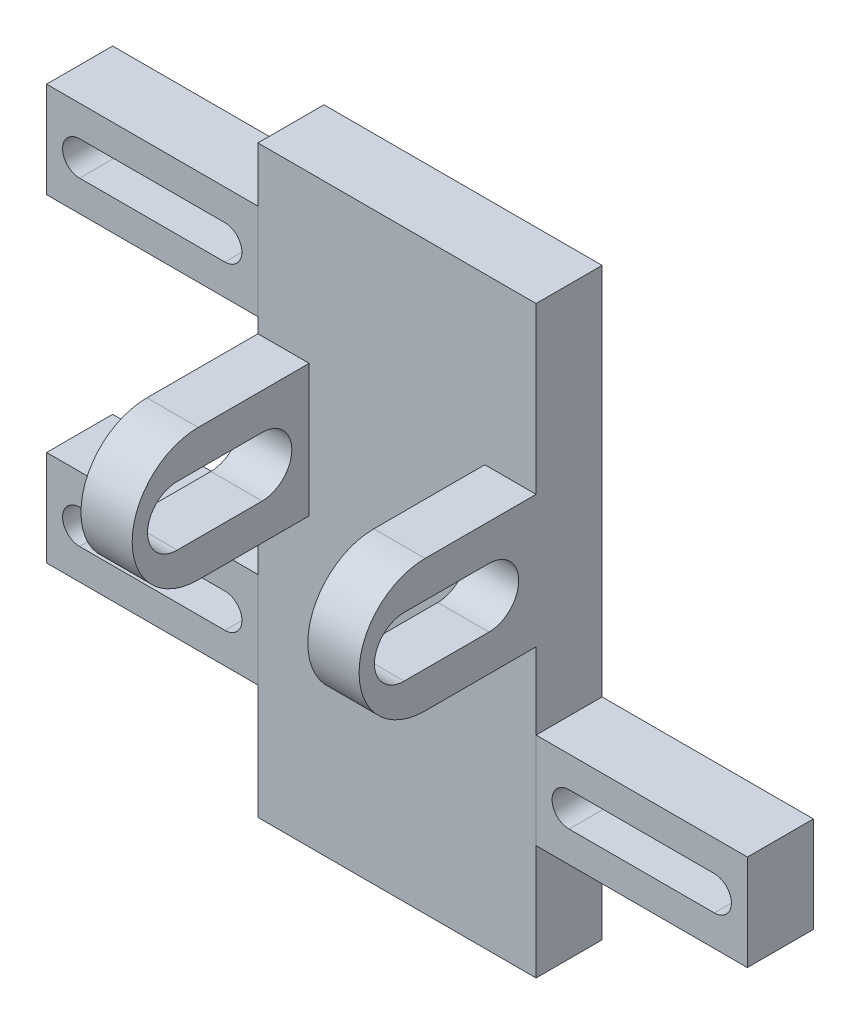
SolidWorks part; units mm, degrees
ref_plane "Front Plane" through (0, 0, 0) normal (0, 0, 1) x (1, 0, 0)
ref_plane "Top Plane" through (0, 0, 0) normal (0, 1, 0) x (1, 0, 0)
ref_plane "Right Plane" through (0, 0, 0) normal (1, 0, 0) x (0, 0, -1)
sketch "Sketch1" plane through (0, 0, 0) normal (0, 0, 1) x (1, 0, 0)
  line L0 (4692.3212, -62.8445) -> (4650.9212, -62.8445) construction
  line L1 (4661.0828, -18.6148) -> (4682.1433, -18.6148)
  line L2 (4661.0828, -18.6148) -> (4661.0828, -62.8445)
  line L3 (4661.0828, -62.8445) -> (4682.1433, -62.8445)
  line L4 (4682.1433, -18.6148) -> (4682.1433, -62.8445)
  line L5 (4661.0828, -27.1456) -> (4658.9212, -27.1456) construction
  line L6 (4658.9212, -12.4285) -> (4658.9212, -50.5381) construction
  line L7 (4682.1433, -34.3161) -> (4684.3037, -34.2412) construction
  line L8 (4684.3037, -50.5381) -> (4684.3037, -12.4285) construction
extrude "Boss-Extrude1" add sketch "Sketch1" along normal blind 5
sketch "Sketch2" plane through (0, 0, 0) normal (0, 0, -1) x (-1, 0, 0)
  line L0 (-4671.6212, -59.6913) -> (-4671.6212, -53.6913) construction
  line L1 (-4664.1212, -59.6913) -> (-4679.1212, -59.6913) construction
  line L2 (-4679.1212, -53.6913) -> (-4664.1212, -53.6913) construction
  line L4 (-4674.1212, -53.8163) -> (-4669.1212, -53.8163)
  line L5 (-4674.1212, -53.8163) -> (-4674.1212, -59.5663)
  line L6 (-4674.1212, -59.5663) -> (-4669.1212, -59.5663)
  line L7 (-4669.1212, -53.8163) -> (-4669.1212, -59.5663)
  line L8 (-4674.1212, -53.8163) -> (-4669.1212, -59.5663) construction
  line L9 (-4674.1212, -59.5663) -> (-4669.1212, -53.8163) construction
  point P6 (-4671.6212, -56.6913)
  dimension "D1" = 5.75
  dimension "D2" = 5
sketch "Sketch4" plane through (4661.0828, 0, 0) normal (-1, 0, 0) x (0, 0, 1)
  line L3 (5, -18.6148) -> (5, -62.8445) construction
  line L4 (13.4005, -31.1292) -> (5, -31.1292)
  line L6 (13.4005, -41.1292) -> (5, -41.1292)
  line L7 (5, -31.1292) -> (5, -41.1292)
  arc A0 (13.4005, -41.1292) -> (13.4005, -31.1292) centre (13.4005, -36.1292) ccw
  dimension "D1" = 5
extrude "Boss-Extrude3" add sketch "Sketch4" against normal blind 3.8801
sketch "Sketch5" plane through (4664.9629, 0, 0) normal (1, 0, 0) x (0, 0, -1)
  line L0 (-14.9864, -36.1292) -> (-8.5634, -36.1292) construction
  line L1 (-14.9864, -33.8792) -> (-8.5634, -33.8792)
  line L2 (-14.9864, -38.3792) -> (-8.5634, -38.3792)
  line L3 (-13.4005, -36.1292) -> (-8.9343, -36.1292) construction
  arc A1 (-14.9864, -33.8792) -> (-14.9864, -38.3792) centre (-14.9864, -36.1292) ccw
  arc A2 (-8.5634, -38.3792) -> (-8.5634, -33.8792) centre (-8.5634, -36.1292) ccw
  point P3 (-11.7749, -36.1292)
  dimension "D1" = 2.25
  dimension "D2" = 1.6257
  dimension "D3" = 4.8372
extrude "Cut-Extrude1" cut sketch "Sketch5" against normal blind 8
ref_plane "Plane1" through (4671.6131, 0, 0) normal (-1, 0, 0) x (0, 0, 1)
mirror "Mirror2" about plane through (4671.6131, 0, 0) normal (-1, 0, 0) of "Cut-Extrude1", "Boss-Extrude3"
sketch "Sketch6" plane through (0, 0, 5) normal (0, 0, 1) x (1, 0, 0)
  line L0 (4688.3131, -48.9131) -> (4688.3131, -52.1631) construction
  line L1 (4682.1433, -46.9131) -> (4698.1433, -46.9131)
  line L2 (4682.1433, -46.9131) -> (4682.1433, -54.1631)
  line L3 (4682.1433, -54.1631) -> (4698.1433, -54.1631)
  line L4 (4698.1433, -46.9131) -> (4698.1433, -54.1631)
  line L5 (4658.9131, -50.5381) -> (4684.2955, -50.5381) construction
  line L6 (4688.3131, -52.1631) -> (4688.3131, -54.1631) construction
  line L7 (4688.3131, -48.9131) -> (4688.3131, -46.9131) construction
  line L8 (4658.4131, -50.5381) -> (4684.8131, -50.5381) construction
  line L9 (4695.6433, -50.5381) -> (4684.6433, -50.5381) construction
  line L10 (4695.6433, -51.828) -> (4684.6433, -51.828)
  line L11 (4695.6433, -49.2483) -> (4684.6433, -49.2483)
  line L12 (4686.6881, -50.5381) -> (4689.9381, -50.5381) construction
  line L13 (4695.6433, -51.828) -> (4698.1433, -51.828) construction
  line L14 (4682.1433, -62.8445) -> (4682.1433, -41.1292) construction
  line L15 (4661.0828, -18.6148) -> (4661.0828, -31.1292) construction
  line L16 (4682.1433, -18.6148) -> (4661.0828, -18.6148) construction
  arc A1 (4695.6433, -51.828) -> (4695.6433, -49.2483) centre (4695.6433, -50.5381) ccw
  arc A2 (4684.6433, -49.2483) -> (4684.6433, -51.828) centre (4684.6433, -50.5381) ccw
  circle A3 centre (4688.3131, -50.5381) radius 1.625 construction
  point P18 (4690.1433, -50.5381)
  dimension "D2" = 16
  dimension "D3" = 11
  dimension "D1" = 1.2898
  dimension "D4" = 2.5
  dimension "D5" = 27.2303
  dimension "D6" = 28.2983
  dimension "D7" = 35.5483
extrude "Boss-Extrude4" add sketch "Sketch6" against normal blind 5 separate body
ref_plane "Plane2" through (4671.6131, 0, 0) normal (-1, 0, 0) x (0, 0, 1)
mirror "Mirror3" about plane through (4671.6131, 0, 0) normal (-1, 0, 0) of bodies 107
ref_plane "Plane3" through (0, -24.872, 0) normal (0, -1, 0) x (-1, 0, 0)
sketch "Sketch9" plane through (0, 0, 5) normal (0, 0, 1) x (1, 0, 0)
  line L0 (4671.6131, -62.8445) -> (4671.6131, -18.6148) construction
  line L1 (4661.0828, -62.8445) -> (4682.1433, -62.8445) construction
  line L2 (4682.1433, -18.6148) -> (4661.0828, -18.6148) construction
  line L3 (4671.6131, -40.7297) -> (4677.5932, -40.7297) construction
ref_plane "Plane4" through (0, -40.7297, 0) normal (0, -1, 0) x (-1, 0, 0)
sketch "Sketch10" plane through (0, 0, 5) normal (0, 0, 1) x (1, 0, 0)
  line L0 (4654.9131, -26.3852) -> (4654.9131, -50.5381) construction
  line L1 (4654.9131, -38.4617) -> (4652.351, -38.4617) construction
ref_plane "Plane5" through (0, -38.4617, 0) normal (0, -1, 0) x (-1, 0, 0)
mirror "Mirror4" about plane through (0, -38.4617, 0) normal (0, -1, 0) of bodies 109 107
sketch "Sketch11" plane through (0, 0, 5) normal (0, 0, 1) x (1, 0, 0)
  line L1 (4682.1433, -22.7602) -> (4698.1433, -22.7602)
  line L2 (4682.1433, -22.7602) -> (4682.1433, -30.0102)
  line L3 (4682.1433, -30.0102) -> (4698.1433, -30.0102)
  line L4 (4698.1433, -22.7602) -> (4698.1433, -30.0102)
extrude "Cut-Extrude2" cut sketch "Sketch11" against normal up to vertex (5 mm away) up to point (4682.1433, -22.7602, 0)
